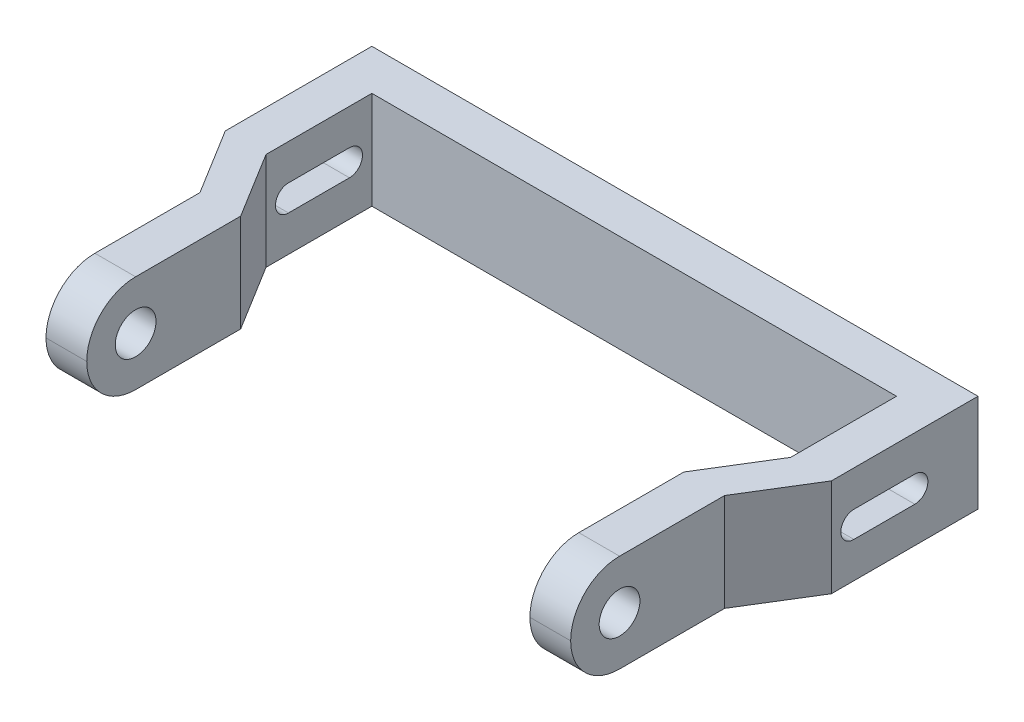
SolidWorks part; units mm, degrees
ref_plane "Plan de face" through (0, 0, 0) normal (0, 0, 1) x (1, 0, 0)
ref_plane "Plan de dessus" through (0, 0, 0) normal (0, 1, 0) x (1, 0, 0)
ref_plane "Plan de droite" through (0, 0, 0) normal (1, 0, 0) x (0, 0, -1)
sketch "Esquisse1" plane through (0, 0, 0) normal (0, 1, 0) x (1, 0, 0)
  line L1 (-27.2, 0) -> (-32.2, 0)
  line L2 (-32.2, 0) -> (-32.2, -2.2564)
  line L5 (-37.2, 45) -> (37.2, 45)
  line L7 (32.2, 40) -> (-32.2, 40)
  line L8 (-32.2, 40) -> (-32.2, 27.0068)
  line L9 (-32.2, 27.0068) -> (-27.2, 18.8954)
  line L10 (-27.2, 18.8954) -> (-27.2, 0)
  line L11 (-32.2, 27.0068) -> (-32.2, 18.8954) construction
  line L12 (-32.2, 18.8954) -> (-32.2, 0)
  line L13 (-37.2, 45) -> (-37.2, 27.0068)
  line L14 (-37.2, 27.0068) -> (-32.2, 18.8954)
  line L15 (0, -55) -> (0, 55) construction
  line L16 (37.2, 45) -> (37.2, 27.0068)
  line L17 (32.2, 40) -> (32.2, 27.0068)
  line L18 (32.2, 27.0068) -> (27.2, 18.8954)
  line L19 (37.2, 27.0068) -> (32.2, 18.8954)
  line L20 (27.2, 18.8954) -> (27.2, 0)
  line L21 (32.2, 18.8954) -> (32.2, 0)
  line L22 (27.2, 0) -> (32.2, 0)
  point P4 (0, 0)
  dimension "D1" = 54.4
  dimension "D4" = 5
  dimension "D5" = 5
extrude "Boss.-Extru.1" add sketch "Esquisse1" along normal blind 12 contours L11 L8 L7 L17 L18 L20 L22 L21 L19 L16 L5 L13 L14 | L9 L11 L12 L1 L10 region at (-29.8473, 0, -11.595) region at (-33.9598, 0, -23.4073)
sketch "Esquisse2" plane through (-32.2, 0, 0) normal (-1, 0, 0) x (0, 0, 1)
  line L0 (0, 6) -> (-18.8954, 6) construction
  line L1 (0, 12) -> (0, 0) construction
  line L2 (-18.8954, 12) -> (-18.8954, 0) construction
  circle A0 centre (-6, 6) radius 2.5
  dimension "D1" = 6
extrude "Enlèv. mat.-Extru.1" cut sketch "Esquisse2" against normal through all
sketch "Esquisse5" plane through (-37.2, 0, 0) normal (-1, 0, 0) x (0, 0, 1)
  line L0 (-27.0068, 6) -> (-40.0068, 6) construction
  line L2 (-27.0068, 12) -> (-27.0068, 0) construction
  line L3 (-37.2476, 6) -> (-29.7659, 6) construction
  line L4 (-37.2476, 7.6) -> (-29.7659, 7.6)
  line L5 (-37.2476, 4.4) -> (-29.7659, 4.4)
  arc A0 (-37.2476, 7.6) -> (-37.2476, 4.4) centre (-37.2476, 6) ccw
  arc A1 (-29.7659, 4.4) -> (-29.7659, 7.6) centre (-29.7659, 6) ccw
  point P6 (-33.5068, 6)
  dimension "D1" = 13
  dimension "D2" = 3.2
extrude "Enlèv. mat.-Extru.2" cut sketch "Esquisse5" against normal through all
fillet "Congé1" radius 6 4 edges at (-29.7, 0, 0) (-29.7, 12, 0) (29.7, 0, 0) (29.7, 12, 0)
